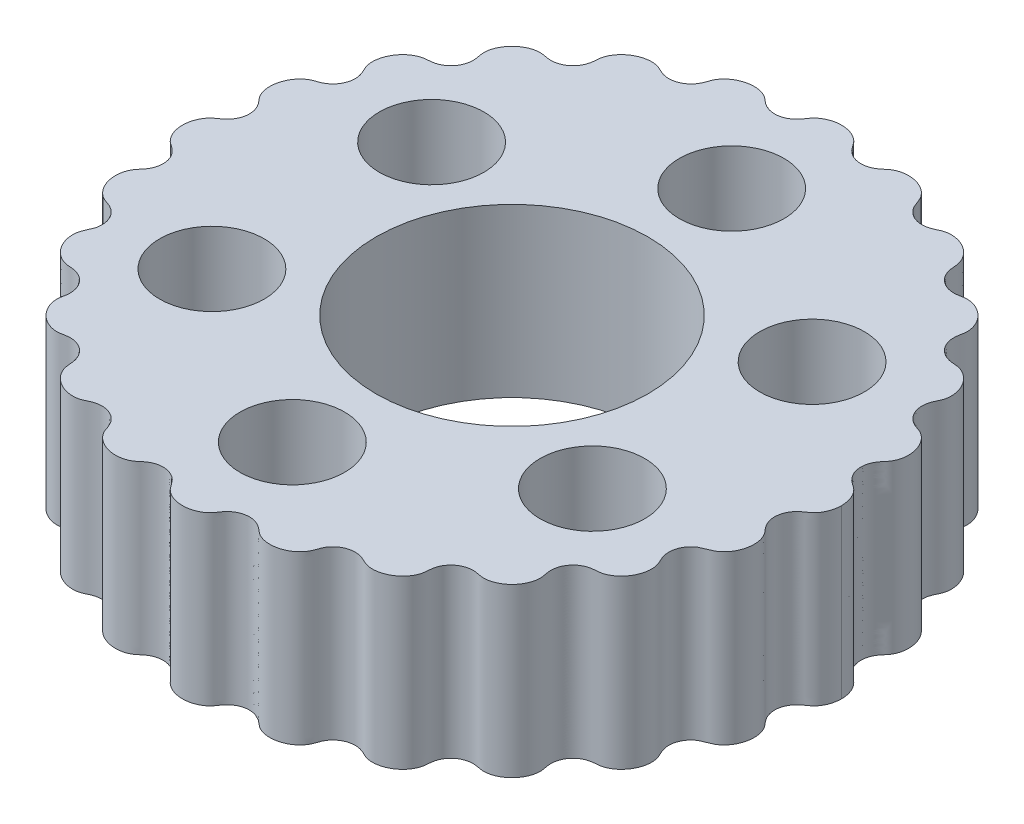
SolidWorks part; units mm, degrees
ref_plane "Front Plane" through (0, 0, 0) normal (0, 0, 1) x (1, 0, 0)
ref_plane "Top Plane" through (0, 0, 0) normal (0, 1, 0) x (1, 0, 0)
ref_plane "Right Plane" through (0, 0, 0) normal (1, 0, 0) x (0, 0, -1)
sketch "Sketch2" plane through (0, 0, 0) normal (0, 1, 0) x (1, 0, 0)
  line L0 (-33.5, 0) -> (33.5, 0) construction
  spline S0 degree 4 number of poles 417 (32.3493, -8.7043) -> (-32.3493, -8.7043) construction
  spline S1 degree 4 number of poles 341 (33.5, 0) -> (-33.5, 0) construction
  spline S2 degree 4 number of poles 341 (33.5, 0) -> (-33.5, 0) construction
  spline S3 degree 1 poles (31.5, 0) (-31.5, 0) knots 0 0 1 1 construction
  spline S4 degree 1 poles (31.5, 0) (-31.5, 0) knots 0 0 1 1 construction
  spline S5 degree 3 number of poles 498 (31.5, 0) -> (-31.5, 0)
  spline S6 degree 3 number of poles 498 (-31.5, 0) -> (31.5, 0)
  dimension "D1" = 2
extrude "Boss-Extrude1" add sketch "Sketch2" along normal blind 16
sketch "Sketch3" plane through (0, 16, 0) normal (0, 1, 0) x (1, 0, 0)
  circle A0 centre (0, 0) radius 13
  circle A1 centre (0, 0) radius 21 construction
  circle A2 centre (0, 21) radius 5
  circle A3 centre (18.1865, 10.5) radius 5
  circle A4 centre (18.1865, -10.5) radius 5
  circle A5 centre (0, -21) radius 5
  circle A6 centre (-18.1865, -10.5) radius 5
  circle A7 centre (-18.1865, 10.5) radius 5
  point P19 (0, 0)
  dimension "D1" = 26
  dimension "D2" = 42
  dimension "D3" = 10
  dimension "D4" = 6
extrude "Cut-Extrude1" cut sketch "Sketch3" against normal through all
